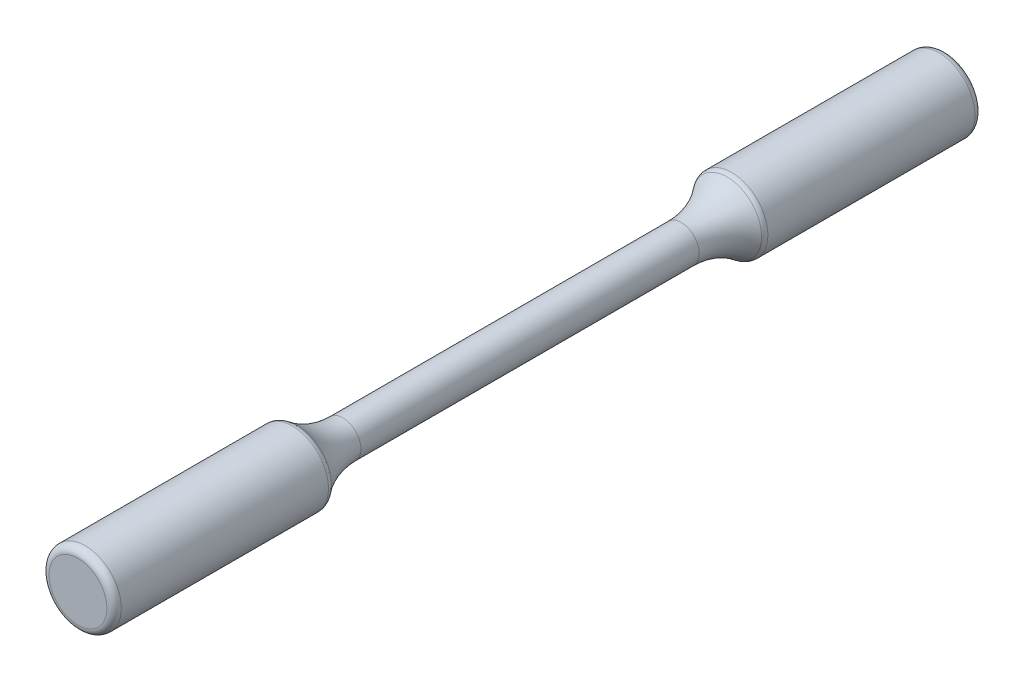
SolidWorks part; units mm, degrees
ref_plane "前基準面" through (0, 0, 0) normal (0, 0, 1) x (1, 0, 0)
ref_plane "上基準面" through (0, 0, 0) normal (0, 1, 0) x (1, 0, 0)
ref_plane "右基準面" through (0, 0, 0) normal (1, 0, 0) x (0, 0, -1)
sketch "草圖1" plane through (0, 0, 0) normal (0, 0, 1) x (1, 0, 0)
  circle A0 centre (0, 0) radius 2.5
  dimension "D1" = 5
extrude "填料-伸長1" add sketch "草圖1" along normal blind 60
sketch "草圖2" plane through (0, 0, 60) normal (0, 0, 1) x (1, 0, 0)
  circle A0 centre (0, 0) radius 5
  dimension "D1" = 10
extrude "填料-伸長2" add sketch "草圖2" along normal blind 30
sketch "草圖3" plane through (0, 0, 0) normal (0, 0, -1) x (-1, 0, 0)
  circle A0 centre (0, 0) radius 5
  dimension "D1" = 10
extrude "填料-伸長3" add sketch "草圖3" along normal blind 30
fillet "圓角2" radius 10 2 edges at (2.5, 0, 0) (2.5, 0, 60)
fillet "圓角3" radius 1 2 edges at (-5, 0, -30) (5, 0, 90)
fillet "圓角4" radius 1 2 edges at (-5, 0, 0) (5, 0, 60)
